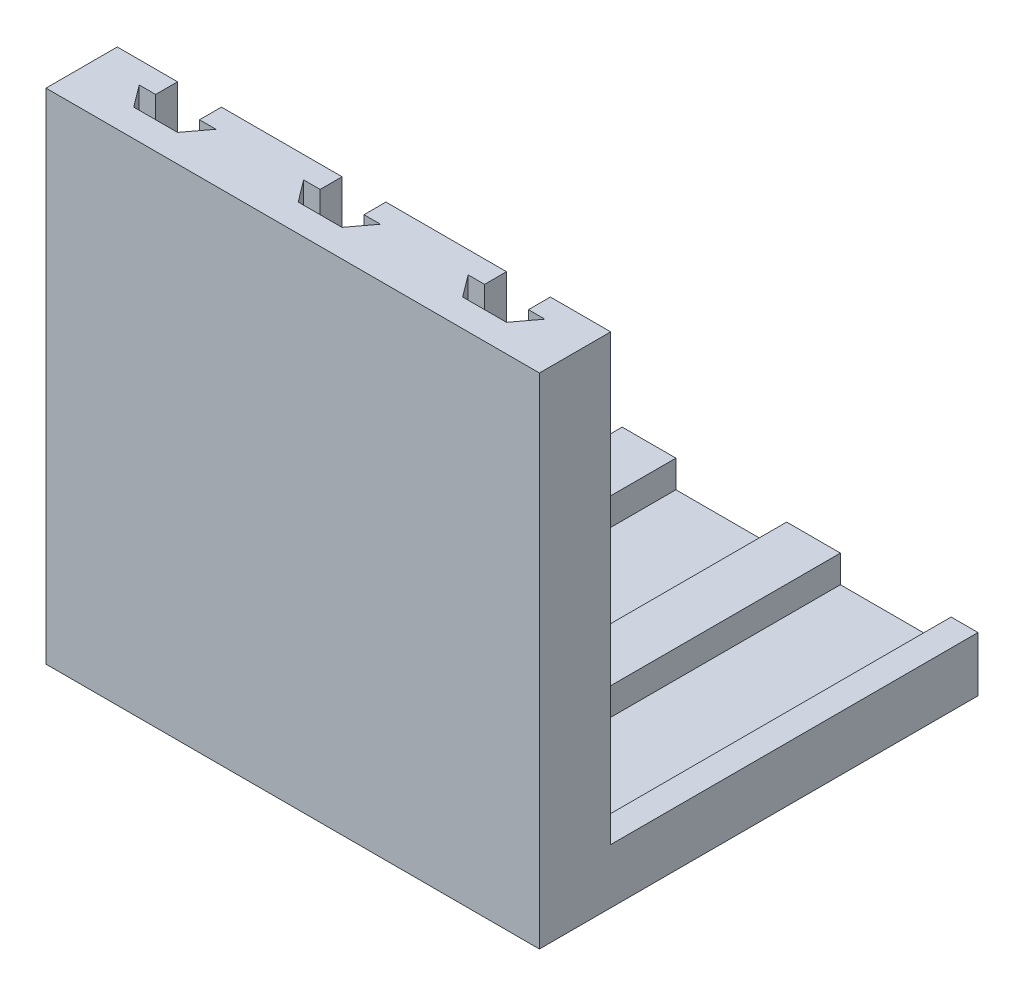
SolidWorks part; units mm, degrees
ref_plane "Front Plane" through (0, 0, 0) normal (0, 0, 1) x (1, 0, 0)
ref_plane "Top Plane" through (0, 0, 0) normal (0, 1, 0) x (1, 0, 0)
ref_plane "Right Plane" through (0, 0, 0) normal (1, 0, 0) x (0, 0, -1)
sketch "Sketch1" plane through (0, 0, 0) normal (0, 1, 0) x (1, 0, 0)
  line L1 (-15, -40) -> (15, -40)
  line L2 (-15, -40) -> (-15, 40)
  line L3 (-15, 40) -> (15, 40)
  line L4 (15, -40) -> (15, 40)
  line L5 (-15, -40) -> (15, 40) construction
  line L6 (-15, 40) -> (15, -40) construction
  point P0 (0, 0)
  dimension "D1" = 80
  dimension "D2" = 30
extrude "Boss-Extrude1" add sketch "Sketch1" along normal blind 10
sketch "Sketch2" plane through (0, 10, 0) normal (0, 1, 0) x (1, 0, 0)
  line L0 (15, -40) -> (15, 40) construction
  line L1 (-15, -40) -> (15, -40)
  line L2 (-15, -40) -> (-15, -27)
  line L3 (-15, -27) -> (15, -27)
  line L4 (15, -40) -> (15, -27)
  dimension "D1" = 13
extrude "Boss-Extrude2" add sketch "Sketch2" along normal blind 81 contours L3 L4 L1 L2
sketch "Sketch3" plane through (0, 91, 0) normal (0, 1, 0) x (1, 0, 0)
  line L0 (0, -27) -> (0, -40) construction
  line L1 (-15, -27) -> (15, -27) construction
  line L2 (-15, -40) -> (15, -40) construction
  line L3 (-4, -27) -> (4, -27)
  line L5 (-15, -27) -> (15, -27) construction
  line L6 (-4, -27) -> (-4, -31)
  line L7 (-4, -31) -> (-7, -31)
  line L8 (-7, -31) -> (-4, -35)
  line L9 (-4, -35) -> (4, -35)
  line L10 (4, -35) -> (7, -31)
  line L11 (7, -31) -> (4, -31)
  line L12 (4, -31) -> (4, -27)
  dimension "D1" = 8
  dimension "D2" = 4
  dimension "D3" = 4
  dimension "D4" = 3
extrude "Cut-Extrude1" cut sketch "Sketch3" against normal blind 40
sketch "Sketch4" plane through (0, 10, 0) normal (0, 1, 0) x (1, 0, 0)
  line L0 (0, 40) -> (0, -27) construction
  line L1 (15, 40) -> (-15, 40) construction
  line L2 (15, -27) -> (15, 40) construction
  line L3 (-15, -27) -> (15, -27) construction
  line L4 (-10.1, 40) -> (10.1, 40)
  line L5 (-10.1, 40) -> (-10.1, -27)
  line L7 (10.1, 40) -> (10.1, -27)
  line L8 (4, -27) -> (15, -27) construction
  line L10 (10.1, -27) -> (-10.1, -27)
  line L11 (-15, 40) -> (-15, -27) construction
  dimension "D1" = 20.2
  dimension "D2" = 4.9
extrude "Cut-Extrude2" cut sketch "Sketch4" against normal blind 5
sketch "Sketch5" plane through (0, 51, 0) normal (0, 1, 0) x (1, 0, 0)
  line L0 (0, -27) -> (0, -35) construction
  line L1 (4, -27) -> (-4, -27) construction
  line L2 (-4, -35) -> (4, -35) construction
  line L3 (4, -31) -> (4, -27) construction
  line L4 (-4, -27) -> (4, -27)
  line L5 (-4, -27) -> (-4, -29)
  line L6 (-4, -29) -> (4, -29)
  line L7 (4, -27) -> (4, -29)
  line L8 (-4, -27) -> (-4, -31) construction
  dimension "D1" = 2
extrude "Cut-Extrude3" cut sketch "Sketch5" against normal blind 51
pattern_linear "LPattern1" count 3 spacing 30 along (-1, 0, 0) of "Boss-Extrude1", "Boss-Extrude2", "Cut-Extrude1", "Cut-Extrude2", "Cut-Extrude3"
